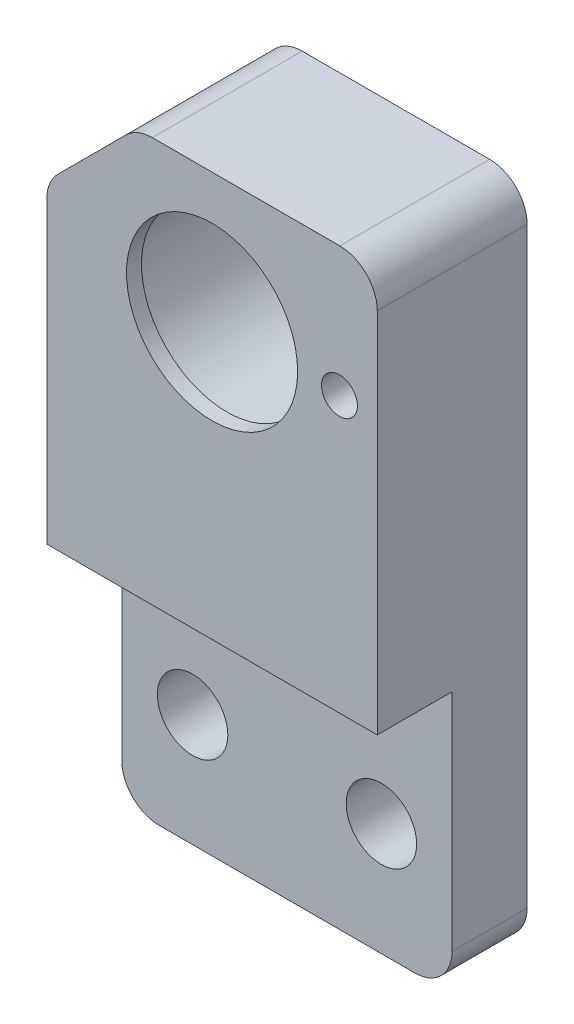
SolidWorks part; units mm, degrees
note: The reader was unsure of these and kept them because the rebuilt part matched: shared geometry of "Sketch1<3>", "Sketch1<4>".
ref_plane "Front Plane" through (0, 0, 0) normal (0, 0, 1) x (1, 0, 0)
ref_plane "Top Plane" through (0, 0, 0) normal (0, 1, 0) x (1, 0, 0)
ref_plane "Right Plane" through (0, 0, 0) normal (1, 0, 0) x (0, 0, -1)
sketch "Sketch1" plane through (0, 0, 0) normal (0, 0, 1) x (1, 0, 0)
  line L79 (214.4949, 63.6705) -> (236.1449, 63.6705)
  line L80 (218.0099, 119.2707) -> (212.2498, 113.5106)
  line L81 (211.3199, 66.8455) -> (211.3199, 111.2655)
  line L82 (211.3199, 85.9006) -> (239.3199, 85.9006)
  line L83 (239.3199, 66.8455) -> (239.3199, 117.0256)
  line L84 (236.1449, 120.2006) -> (220.255, 120.2006)
  circle A89 centre (225.3199, 109.2006) radius 7.9502
  circle A90 centre (225.3199, 109.2006) radius 7.25
  arc A91 (211.3199, 66.8455) -> (214.4949, 63.6705) centre (214.4949, 66.8455) ccw
  arc A92 (236.1449, 63.6705) -> (239.3199, 66.8455) centre (236.1449, 66.8455) ccw
  arc A93 (239.3199, 117.0256) -> (236.1449, 120.2006) centre (236.1449, 117.0256) ccw
  arc A94 (220.255, 120.2006) -> (218.0099, 119.2707) centre (220.255, 117.0256) ccw
  arc A95 (212.2498, 113.5106) -> (211.3199, 111.2655) centre (214.4949, 111.2655) ccw
  circle A96 centre (217.3199, 73.2006) radius 2.9845
  circle A97 centre (233.3199, 73.2006) radius 2.9845
  circle A98 centre (236.1149, 109.2006) radius 1.524
extrude "Boss-Extrude1" add sketch "Sketch1" along normal blind 12.7 contours L79 A92 L83 L82 L81 A91 A97 A96 | L80 A95 L81 L82 L83 A93 L84 A94 A98 A89 | A89 A90
extrude "Cut-Extrude1" cut sketch "Sketch1<3>" along normal blind 11.43 contours A89 A90
sketch "Sketch1<3>" plane through (0, 0, 0) normal (0, 0, 1) x (1, 0, 0) same geometry as "Sketch1"
extrude "Cut-Extrude2" cut sketch "Sketch1<4>" against normal blind 6.35 from offset 12.7 contours L79 A92 L83 L82 L81 A91 A97 A96
sketch "Sketch1<4>" plane through (0, 0, 0) normal (0, 0, 1) x (1, 0, 0) same geometry as "Sketch1"
